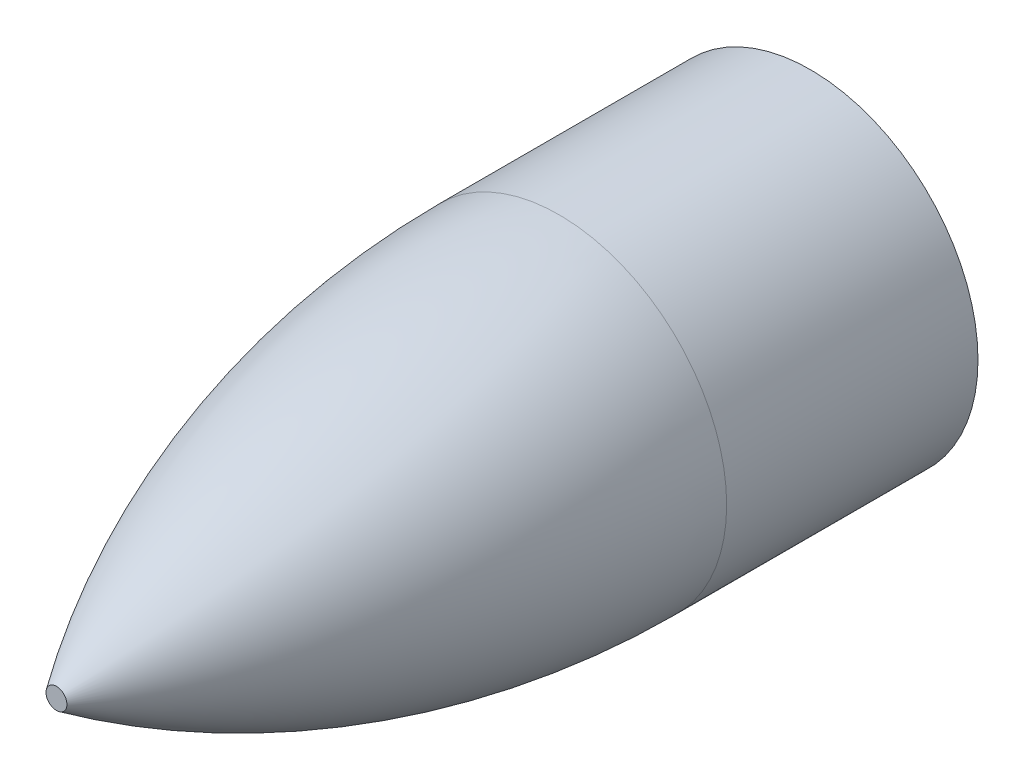
SolidWorks part; units mm, degrees
ref_plane "Front Plane" through (0, 0, 0) normal (0, 0, 1) x (1, 0, 0)
ref_plane "Top Plane" through (0, 0, 0) normal (0, 1, 0) x (1, 0, 0)
ref_plane "Right Plane" through (0, 0, 0) normal (1, 0, 0) x (0, 0, -1)
sketch "Sketch3" plane through (0, 0, 0) normal (1, 0, 0) x (0, 0, -1)
  line L0 (0, 0) -> (152.4, 0)
  line L1 (152.4, 0) -> (152.4, 3.175)
  line L2 (44.45, 0) -> (120.65, 0)
  line L3 (38.1, 12.7) -> (57.15, 12.7)
  line L5 (95.25, 10.3257) -> (152.4, 3.175)
  line L6 (0, 0) -> (0, 0.7937)
  line L7 (120.65, 0) -> (120.65, 3.9688)
  line L8 (120.65, 3.9688) -> (116.6813, 3.9687)
  line L9 (44.45, 9.2075) -> (92.5773, 9.2075)
  line L10 (120.65, 3.175) -> (122.2375, 3.175)
  line L11 (122.2375, 3.175) -> (125.5918, 6.5293)
  line L12 (57.15, 12.7) -> (57.15, 0)
  line L13 (35.2425, 0) -> (35.2425, 14.8815) construction
  arc A1 (57.15, 12.7) -> (95.25, 10.3257) centre (57.15, -294.1784) cw
  arc A2 (0, 0.7937) -> (38.1, 12.7) centre (38.1, -54.2131) cw
  circle A3 centre (44.45, 0) radius 9.2075
  arc A4 (92.5773, 9.2075) -> (113.6217, 4.6337) centre (92.5773, -41.4927) cw
  arc A5 (113.6217, 4.6337) -> (116.6813, 3.9687) centre (116.6813, 11.3399) ccw
  spline S0 degree 3 poles (44.45, 9.2075) (40.7676, 9.2075) (36.1634, 8.1185) (35.2425, 5.0154) (35.2425, 0) knots 0 0 0 0 0.484293 1 1 1 1
  point P24 (37.1719, 7.6803)
  dimension "D1" = 12.7
  dimension "D5" = 57.15
  dimension "D6" = 0.7937
  dimension "D8" = 76.2
  dimension "D9" = 18.415
  dimension "D2" = 38.1
  dimension "D3" = 3.175
  dimension "D4" = 19.05
  dimension "D7" = 152.4
  dimension "D10" = 3.9688
  dimension "D11" = 3.9688
  dimension "D12" = 31.75
  dimension "D13" = 1.5875
  dimension "D14" = 0.7937
  dimension "D15" = 135
revolve "Revolve2" add sketch "Sketch3" angle 360 about L0 region at (0, 4.9852, -21.6045) region at (0, 6.5244, -37.6723) region at (0, 10.6349, -45.2545)
sketch "Sketch4" plane through (0, 0, -57.15) normal (0, 0, -1) x (-1, 0, 0)
  circle A0 centre (0, 0) radius 11.2395
  dimension "D1" = 22.479
extrude "Cut-Extrude1" cut sketch "Sketch4" against normal blind 9.525
ref_plane "Plane1" through (0, 11.43, 0) normal (0, 1, 0) x (1, 0, 0)
sketch "Sketch5" plane through (0, 11.43, 0) normal (0, 1, 0) x (1, 0, 0)
  line L0 (12.7, 57.15) -> (-12.7, 57.15) construction
  line L1 (1.4605, 57.15) -> (-1.4605, 57.15)
  line L2 (1.4605, 57.15) -> (1.4605, 54.229)
  line L3 (1.4605, 54.229) -> (-1.4605, 54.229)
  line L4 (-1.4605, 57.15) -> (-1.4605, 54.229)
  line L5 (1.4605, 57.15) -> (-1.4605, 54.229) construction
  line L6 (1.4605, 54.229) -> (-1.4605, 57.15) construction
  line L7 (-12.7, 57.15) -> (12.7, 57.15) construction
  point P4 (0, 55.6895)
  point P14 (0, 57.15)
  dimension "D1" = 2.921
extrude "Boss-Extrude1" add sketch "Sketch5" against normal blind 1.8415
mirror "Mirror1" about plane through (0, 0, 0) normal (0, 1, 0) of "Boss-Extrude1"
